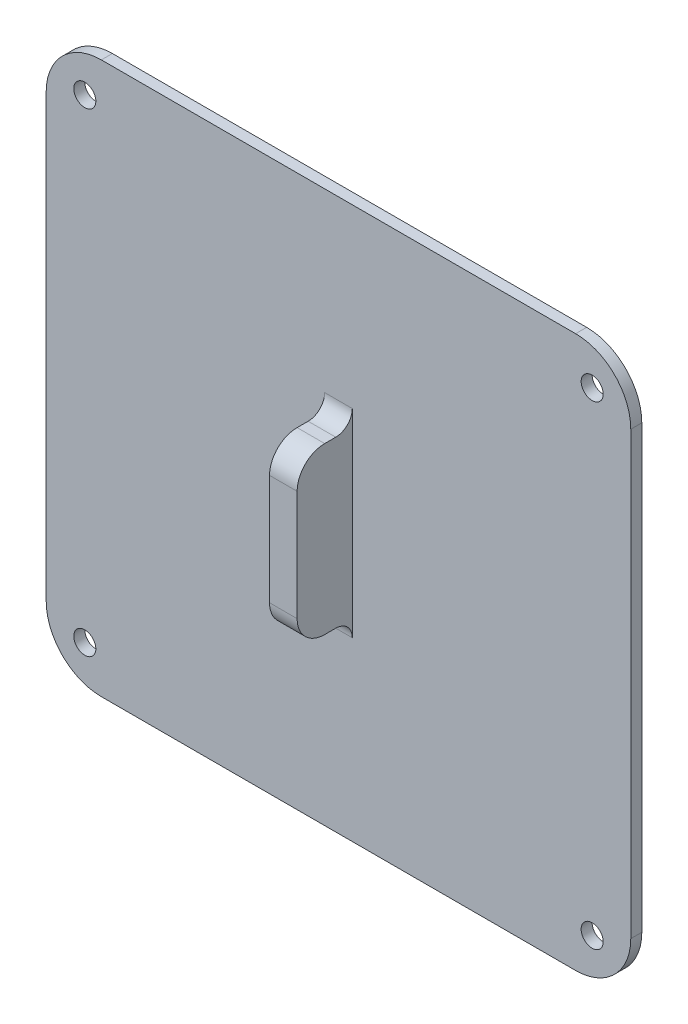
SolidWorks part; units mm, degrees
material "ABS"
ref_plane "Front Plane" through (0, 0, 0) normal (0, 0, 1) x (1, 0, 0)
ref_plane "Top Plane" through (0, 0, 0) normal (0, 1, 0) x (1, 0, 0)
ref_plane "Right Plane" through (0, 0, 0) normal (1, 0, 0) x (0, 0, -1)
sketch "Sketch1" plane through (0, 0, 0) normal (0, 0, 1) x (1, 0, 0)
  line L4 (-43, 260) -> (43, 260)
  line L5 (53, 270) -> (53, 350)
  line L6 (43, 360) -> (-43, 360)
  line L7 (-53, 350) -> (-53, 270)
  arc A4 (43, 260) -> (53, 270) centre (43, 270) ccw
  arc A5 (53, 350) -> (43, 360) centre (43, 350) ccw
  arc A6 (-43, 360) -> (-53, 350) centre (-43, 350) ccw
  arc A7 (-53, 270) -> (-43, 260) centre (-43, 270) ccw
extrude "Boss-Extrude1" add sketch "Sketch1" against normal blind 2
sketch "Sketch2" plane through (0, 0, -2) normal (0, 0, -1) x (-1, 0, 0)
  line L0 (-53, 310) -> (53, 310) construction
  line L1 (-53, 270) -> (-53, 350) construction
  line L2 (53, 350) -> (53, 270) construction
  circle A4 centre (46, 267) radius 2
  circle A6 centre (-46, 267) radius 2
  circle A7 centre (-46, 353) radius 2
  circle A8 centre (46, 353) radius 2
extrude "Cut-Extrude1" cut sketch "Sketch2" against normal blind 3
sketch "Sketch6" plane through (0, 0, 0) normal (0, 0, 1) x (1, 0, 0)
  line L0 (0, 260) -> (0, 360) construction
  line L1 (-43, 260) -> (43, 260) construction
  line L2 (43, 360) -> (-43, 360) construction
  line L3 (-53, 310) -> (53, 310) construction
  line L4 (-2.5, 325) -> (2.5, 325)
  line L5 (-2.5, 325) -> (-2.5, 295)
  line L6 (-2.5, 295) -> (2.5, 295)
  line L7 (2.5, 325) -> (2.5, 295)
  line L8 (-53, 350) -> (-53, 270) construction
  line L9 (53, 270) -> (53, 350) construction
  dimension "D1" = 15
  dimension "D2" = 30
  dimension "D3" = 5
  dimension "D4" = 2.5
extrude "Boss-Extrude2" add sketch "Sketch6" along normal blind 10
fillet "Fillet1" radius 5 2 edges at (0, 325, 10) (0, 295, 10)
fillet "Fillet2" radius 3 2 edges at (0, 295, 0) (0, 325, 0)
